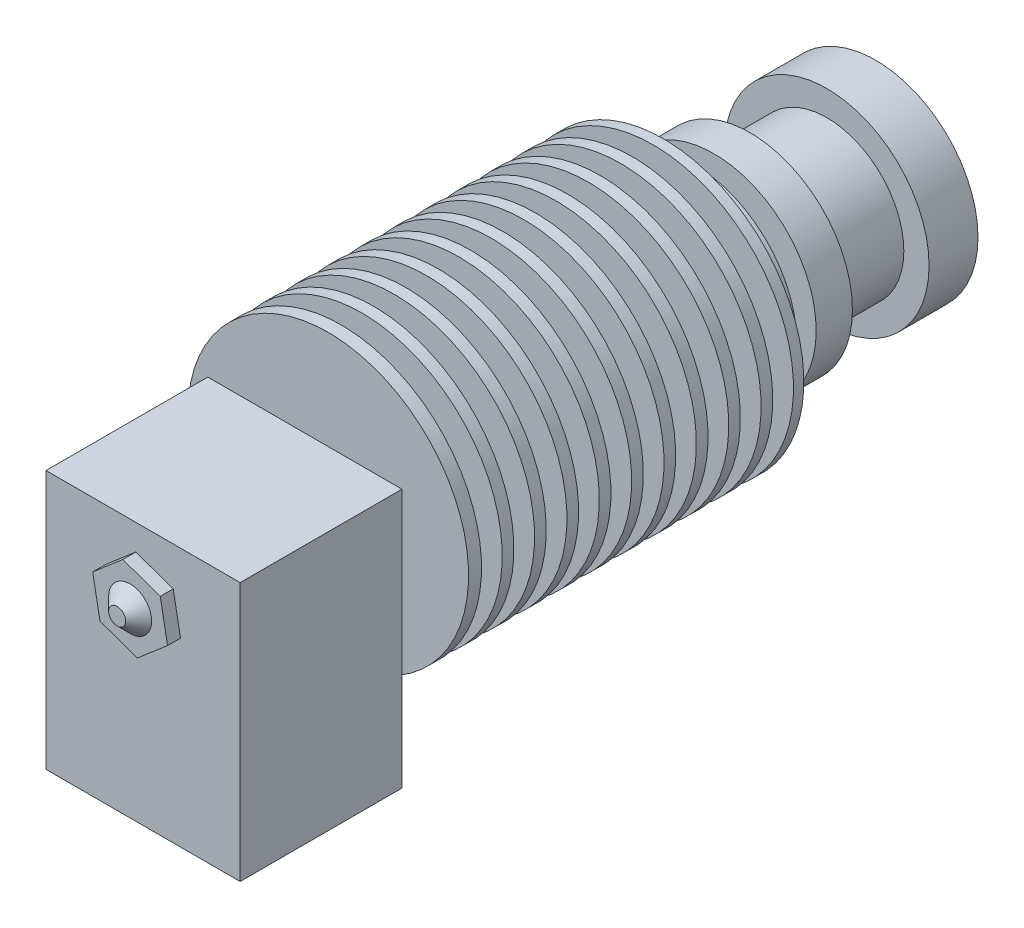
SolidWorks part; units mm, degrees
material "Alliage 1060"
ref_plane "Front Plane" through (0, 0, 0) normal (0, 0, 1) x (1, 0, 0)
ref_plane "Top Plane" through (0, 0, 0) normal (0, 1, 0) x (1, 0, 0)
ref_plane "Right Plane" through (0, 0, 0) normal (1, 0, 0) x (0, 0, -1)
sketch "Sketch1" plane through (0, 0, 0) normal (0, 0, 1) x (1, 0, 0)
  circle A0 centre (0, 0) radius 10.845
  dimension "D1" = 21.69
extrude "Boss-Extrude1" add sketch "Sketch1" along normal blind 25.9
sketch "Sketch2" plane through (0, 0, 0) normal (0, 1, 0) x (1, 0, 0)
  line L0 (10.845, 0) -> (-10.845, 0) construction
  line L1 (-10.845, -25.9) -> (10.845, -25.9) construction
  line L2 (10.845, 0) -> (-10.845, 0) construction
  line L3 (-10.845, -25.9) -> (10.845, -25.9) construction
  line L4 (0, 0) -> (0, -25.9) construction
  line L5 (-10.845, -0.8) -> (-5.5, -0.8)
  line L6 (-10.845, -0.8) -> (-10.845, -2.4)
  line L7 (-10.845, -2.4) -> (-5.5, -2.4)
  line L8 (-5.5, -0.8) -> (-5.5, -2.4)
  dimension "D1" = 11
  dimension "D2" = 1.6
  dimension "D3" = 1.6
ref_axis "Axis1" through (0, 0, 25.9) along (0, 0, -1)
revolve "Cut-Revolve1" cut sketch "Sketch2" angle 360 about L4
pattern_linear "LPattern1" count 10 spacing 2.5 along (0, 0, 1) of "Cut-Revolve1"
sketch "Sketch3" plane through (0, 0, 0) normal (0, 0, -1) x (-1, 0, 0)
  circle A0 centre (0, 0) radius 7.9
  dimension "D1" = 15.8
extrude "Boss-Extrude2" add sketch "Sketch3" along normal blind 16.4
sketch "Sketch4" plane through (0, 0, 0) normal (0, 1, 0) x (1, 0, 0)
  line L0 (7.9, 16.4) -> (-7.9, 16.4) construction
  line L1 (7.9, 0) -> (-7.9, 0) construction
  line L2 (7.9, 16.4) -> (-7.9, 16.4) construction
  line L3 (7.9, 0) -> (-7.9, 0) construction
  line L5 (-7.9, 12.62) -> (-5.95, 12.62)
  line L6 (-7.9, 12.62) -> (-7.9, 6.7)
  line L7 (-7.9, 6.7) -> (-5.95, 6.7)
  line L8 (-5.95, 12.62) -> (-5.95, 6.7)
  line L9 (0, 0) -> (0, 16.4) construction
  line L11 (-7.9, 2.4) -> (-5, 2.4)
  line L12 (-7.9, 2.4) -> (-7.9, 3.9)
  line L13 (-7.9, 3.9) -> (-5, 3.9)
  line L14 (-5, 2.4) -> (-5, 3.9)
  line L15 (-7.9, 1.5) -> (-5, 1.5)
  line L16 (-7.9, 1.5) -> (-7.9, 0)
  line L17 (-7.9, 0) -> (-5, 0)
  line L18 (-5, 1.5) -> (-5, 0)
  dimension "D1" = 2.8
  dimension "D2" = 11.9
  dimension "D3" = 10
  dimension "D4" = 10
  dimension "D5" = 5.92
  dimension "D6" = 0.9
  dimension "D7" = 1.5
  dimension "D8" = 1.5
revolve "Cut-Revolve2" cut sketch "Sketch4" angle 360 about L9
sketch "Sketch5" plane through (0, 0, 25.9) normal (0, 0, 1) x (1, 0, 0)
  circle A0 centre (0, 0) radius 2
  dimension "D1" = 4
extrude "Boss-Extrude3" add sketch "Sketch5" along normal blind 1.8
sketch "Sketch6" plane through (0, 0, 27.7) normal (0, 0, 1) x (1, 0, 0)
  line L1 (-7.5, 5) -> (7.5, 5)
  line L2 (-7.5, 5) -> (-7.5, -15)
  line L3 (-7.5, -15) -> (7.5, -15)
  line L4 (7.5, 5) -> (7.5, -15)
  point P4 (0, 0)
  dimension "D1" = 15
  dimension "D2" = 20
  dimension "D3" = 5
  dimension "D4" = 7.5
extrude "Boss-Extrude4" add sketch "Sketch6" along normal blind 12.5
sketch "Sketch7" plane through (0, 0, 40.2) normal (0, 0, 1) x (1, 0, 0)
  line L1 (2.8914, -1.0185) -> (2.3277, 1.9948)
  line L2 (2.3277, 1.9948) -> (-0.5637, 3.0132)
  line L3 (-0.5637, 3.0132) -> (-2.8914, 1.0185)
  line L4 (-2.8914, 1.0185) -> (-2.3277, -1.9948)
  line L5 (-2.3277, -1.9948) -> (0.5637, -3.0132)
  line L6 (0.5637, -3.0132) -> (2.8914, -1.0185)
  circle A0 centre (0, 0) radius 2 construction
  circle A1 centre (0, 0) radius 2 construction
  circle A2 centre (0, 0) radius 2.6548 construction
extrude "Boss-Extrude5" add sketch "Sketch7" along normal blind 1
sketch "Sketch8" plane through (0, 0, 41.2) normal (0, 0, 1) x (1, 0, 0)
  circle A0 centre (0, 0) radius 1.6593
extrude "Boss-Extrude6" add sketch "Sketch8" along normal blind 1 draft 45
ref_axis "Axis2" through (0, 0, -16.4) along (0, 0, 1)
sketch "Sketch9" plane through (0, 0, -16.4) normal (0, 0, -1) x (-1, 0, 0)
  line L0 (-7.5, 5) -> (7.5, 5) construction
  line L1 (-2.823, 4.8895) -> (-5.6459, 0)
  line L2 (-5.6459, 0) -> (-2.823, -4.8895)
  line L3 (-2.823, -4.8895) -> (2.823, -4.8895)
  line L4 (2.823, -4.8895) -> (5.6459, 0)
  line L5 (5.6459, 0) -> (2.823, 4.8895)
  line L6 (2.823, 4.8895) -> (-2.823, 4.8895)
  circle A0 centre (0, 0) radius 4.8895 construction
  dimension "D1" = 9.779
extrude "Boss-Extrude7" [suppressed] add sketch "Sketch9" along normal blind 9.525
sketch "Sketch10" [suppressed] plane through (0, 0, -25.925) normal (0, 0, -1) x (-1, 0, 0)
  circle A0 centre (0, 0) radius 3.0309
extrude "Boss-Extrude8" [suppressed] add sketch "Sketch10" along normal blind 1.6002
sketch "Sketch11" [suppressed] plane through (0, 0, -27.5252) normal (0, 0, -1) x (-1, 0, 0)
  circle A0 centre (0, 0) radius 4.9784
  dimension "D1" = 9.9568
extrude "Boss-Extrude9" [suppressed] add sketch "Sketch11" along normal blind 1.778
sketch "Sketch12" [suppressed] plane through (0, 0, -29.3032) normal (0, 0, -1) x (-1, 0, 0)
  circle A0 centre (0, 0) radius 2.032
  circle A1 centre (0, 0) radius 1.016
  dimension "D1" = 4.064
  dimension "D2" = 2.032
extrude "Boss-Extrude10" [suppressed] add sketch "Sketch12" along normal blind 5
equation "\"D4@Sketch6\"=\"D1@Sketch6\"/2"
